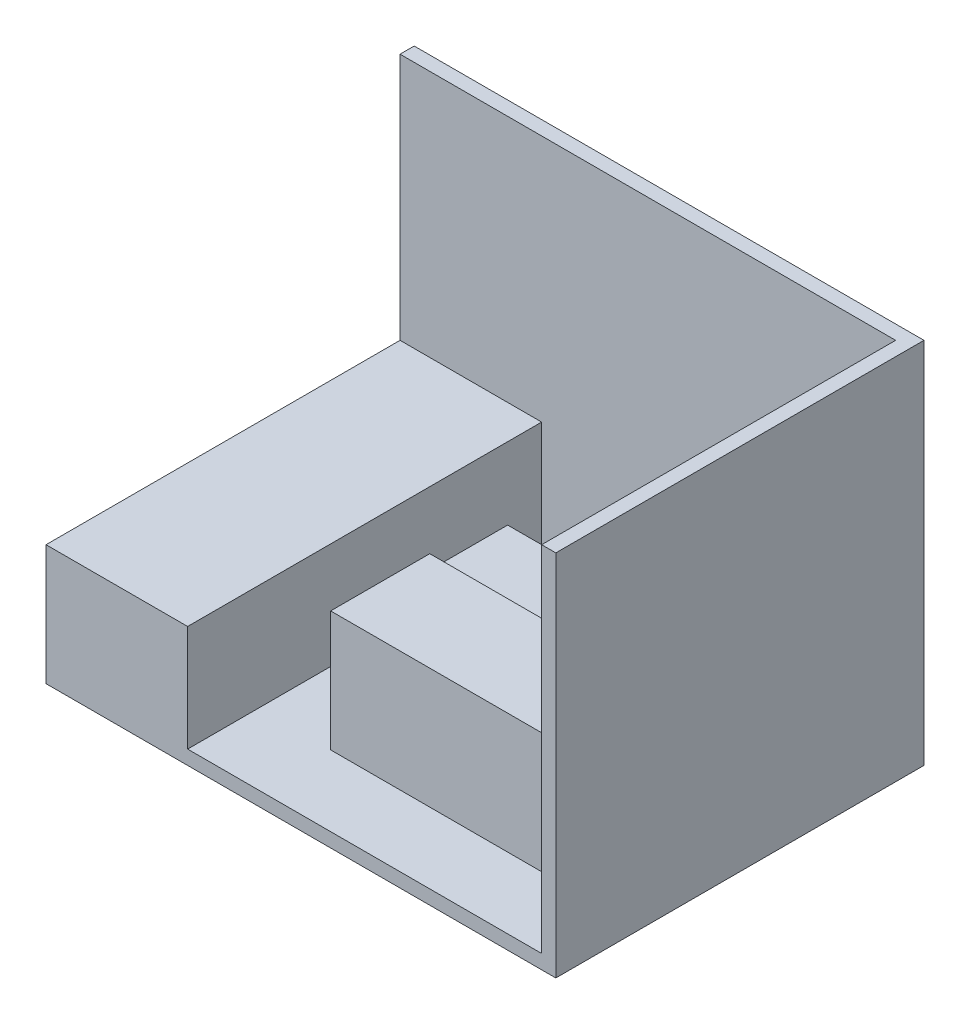
SolidWorks part; units mm, degrees
ref_plane "Front Plane" through (0, 0, 0) normal (0, 0, 1) x (1, 0, 0)
ref_plane "Top Plane" through (0, 0, 0) normal (0, 1, 0) x (1, 0, 0)
ref_plane "Right Plane" through (0, 0, 0) normal (1, 0, 0) x (0, 0, -1)
sketch "Sketch1" plane through (0, 0, 0) normal (0, 1, 0) x (1, 0, 0)
  line L1 (-2246.3768, 1072.4638) -> (1353.6232, 1072.4638)
  line L2 (-2246.3768, 1072.4638) -> (-2246.3768, -1527.5362)
  line L3 (-2246.3768, -1527.5362) -> (1353.6232, -1527.5362)
  line L4 (1353.6232, 1072.4638) -> (1353.6232, -1527.5362)
  dimension "D1" = 3600
  dimension "D2" = 2600
extrude "Boss-Extrude1" add sketch "Sketch1" along normal blind 100
sketch "Sketch2" plane through (0, 100, 0) normal (0, 1, 0) x (1, 0, 0)
  line L0 (1353.6232, -1527.5362) -> (1253.6232, -1527.5362)
  line L1 (-2246.3768, -1527.5362) -> (1353.6232, -1527.5362) construction
  line L2 (1253.6232, -1527.5362) -> (1253.6232, 972.4638)
  line L3 (1253.6232, 972.4638) -> (-2246.3768, 972.4638)
  line L4 (-2246.3768, 1072.4638) -> (-2246.3768, -1527.5362) construction
  line L5 (-2246.3768, 972.4638) -> (-2246.3768, 1072.4638)
  line L6 (-2246.3768, 1072.4638) -> (1353.6232, 1072.4638)
  line L7 (1353.6232, 1072.4638) -> (1353.6232, -1527.5362)
  dimension "D1" = 100
  dimension "D2" = 100
extrude "Boss-Extrude2" add sketch "Sketch2" along normal blind 2500
sketch "Sketch4" plane through (0, 100, 0) normal (0, 1, 0) x (1, 0, 0)
  line L0 (-2246.3768, -1527.5362) -> (1253.6232, -1527.5362) construction
  line L1 (1263.6232, -1027.5362) -> (-736.3768, -1027.5362)
  line L2 (1263.6232, -1027.5362) -> (1263.6232, -327.5362)
  line L3 (1263.6232, -327.5362) -> (-736.3768, -327.5362)
  line L4 (-736.3768, -1027.5362) -> (-736.3768, -327.5362)
  line L6 (1253.6232, 972.4638) -> (1253.6232, -1527.5362) construction
  dimension "D1" = 2000
  dimension "D2" = 700
  dimension "D3" = 500
  dimension "D4" = 10
extrude "Boss-Extrude3" add sketch "Sketch4" along normal blind 850
sketch "Sketch5" plane through (0, 100, 0) normal (0, 1, 0) x (1, 0, 0)
  line L0 (-2246.3768, 972.4638) -> (1253.6232, 972.4638) construction
  line L1 (-2246.3768, -1527.5362) -> (-1246.3768, -1527.5362)
  line L2 (-2246.3768, -1527.5362) -> (-2246.3768, 972.4638)
  line L3 (-2246.3768, 972.4638) -> (-1246.3768, 972.4638)
  line L4 (-1246.3768, -1527.5362) -> (-1246.3768, 972.4638)
  dimension "D1" = 1000
extrude "Boss-Extrude4" add sketch "Sketch5" along normal blind 750
sketch "Sketch6" plane through (0, 100, 0) normal (0, 1, 0) x (1, 0, 0)
  line L0 (1253.6232, -327.5362) -> (-736.3768, -327.5362) construction
  line L1 (-736.3768, -277.5362) -> (263.6232, -277.5362)
  line L2 (-736.3768, -277.5362) -> (-736.3768, 222.4638)
  line L3 (-736.3768, 222.4638) -> (263.6232, 222.4638)
  line L4 (263.6232, -277.5362) -> (263.6232, 222.4638)
  dimension "D1" = 500
  dimension "D2" = 1000
  dimension "D3" = 50
extrude "Boss-Extrude5" add sketch "Sketch6" along normal blind 750
